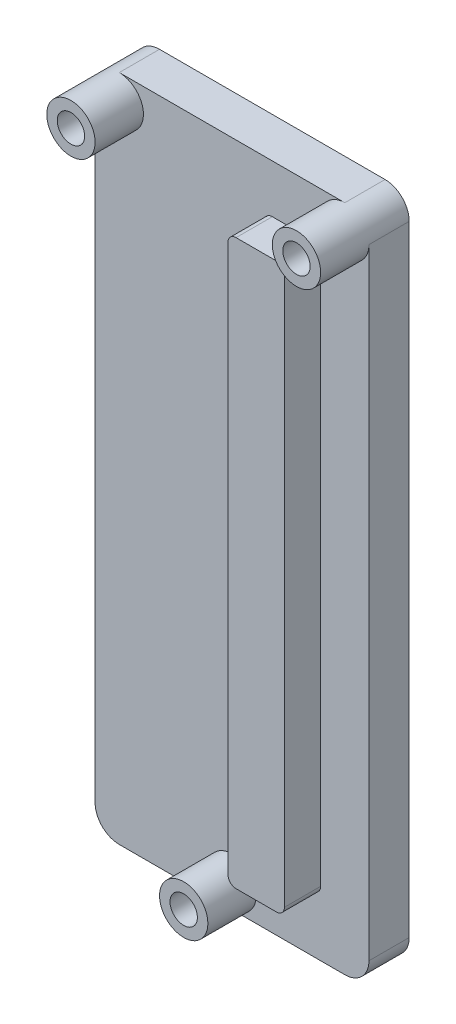
SolidWorks part; units mm, degrees
ref_plane "Plan de face" through (0, 0, 0) normal (0, 0, 1) x (1, 0, 0)
ref_plane "Plan de dessus" through (0, 0, 0) normal (0, 1, 0) x (1, 0, 0)
ref_plane "Plan de droite" through (0, 0, 0) normal (1, 0, 0) x (0, 0, -1)
sketch "Esquisse1" plane through (0, 0, 0) normal (0, 0, 1) x (1, 0, 0)
  line L1 (3, 0) -> (31, 0)
  line L2 (0, 3) -> (0, 80)
  line L3 (3, 83) -> (31, 83)
  line L4 (34, 3) -> (34, 80)
  arc A7 (3, 0) -> (0, 3) centre (3, 3) cw
  arc A8 (31, 0) -> (34, 3) centre (31, 3) ccw
  arc A9 (34, 80) -> (31, 83) centre (31, 80) ccw
  arc A10 (0, 80) -> (3, 83) centre (3, 80) cw
  point P2 (0, 0)
  point P7 (0, 0)
  point P9 (34, 0)
  point P10 (34, 0)
  point P15 (0, 83)
  point P18 (0, 83)
  dimension "D3" = 3
  dimension "D1" = 83
  dimension "D2" = 34
extrude "Boss.-Extru.2" add sketch "Esquisse1" along normal blind 5
sketch "Esquisse4" plane through (0, 0, 5) normal (0, 0, 1) x (1, 0, 0)
  line L0 (0, 80) -> (0, 3) construction
  line L3 (34, 3) -> (34, 80) construction
  line L4 (31, 83) -> (3, 83) construction
  circle A0 centre (3, 80) radius 3
  circle A1 centre (31, 80) radius 3
  circle A2 centre (17, 3) radius 3
  point P8 (16, 3.8141)
  point P11 (0, 0)
  dimension "D1" = 17
  dimension "D2" = 77
  dimension "D3" = 28
  dimension "D4" = 3
  dimension "D5" = 3
  dimension "D6" = 3
extrude "Boss.-Extru.3" add sketch "Esquisse4" along normal blind 6
hole_wizard "Dégagement M31" positions "Esquisse5" profile "Esquisse6" hole size "M3" standard "ISO" end condition through all
sketch "Esquisse5" plane through (0, 0, 11) normal (0, 0, 1) x (1, 0, 0)
  point P0 (3, 80)
  point P3 (31, 80)
  point P6 (17, 3)
sketch "Esquisse6" plane through (3, 80, 11) normal (1, 0, 0) x (0, -1, 0)
  line L0 (0, 0) -> (0, 11)
  line L1 (0, 11) -> (1.7, 11)
  line L2 (1.7, 11) -> (1.7, 0)
  line L5 (1.7, 0) -> (0, 0)
  line L11 (0, -6.35) -> (0, 107.95) construction
  dimension "Diamètre du perçage jusqu'au prochain" = 3.4
  dimension "Profondeur du perçage jusqu'au prochain" = 11
sketch "Esquisse2" plane through (0, 0, 5) normal (0, 0, 1) x (1, 0, 0)
  line L1 (22, 77) -> (27, 77)
  line L2 (21, 76) -> (21, 8)
  line L3 (22, 7) -> (27, 7)
  line L4 (28, 76) -> (28, 8)
  line L9 (31, 83) -> (3, 83) construction
  line L10 (34, 3) -> (34, 80) construction
  arc A2 (21, 8) -> (22, 7) centre (22, 8) ccw
  arc A3 (27, 7) -> (28, 8) centre (27, 8) ccw
  arc A4 (27, 77) -> (28, 76) centre (27, 76) cw
  arc A5 (22, 77) -> (21, 76) centre (22, 76) ccw
  point P25 (24.5, 7)
  dimension "D1" = 6
  dimension "D3" = 70
  dimension "D7" = 7
  dimension "D8" = 6
extrude "Boss.-Extru.4" add sketch "Esquisse2" along normal blind 4.5
